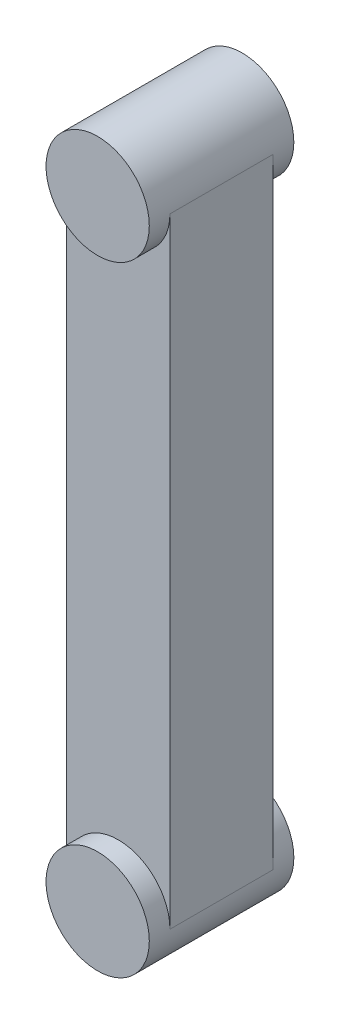
SolidWorks part; units mm, degrees
material "普通碳钢"
ref_plane "前视基准面" through (0, 0, 0) normal (0, 0, 1) x (1, 0, 0)
ref_plane "上视基准面" through (0, 0, 0) normal (0, 1, 0) x (1, 0, 0)
ref_plane "右视基准面" through (0, 0, 0) normal (1, 0, 0) x (0, 0, -1)
sketch "草图1" plane through (0, 0, 0) normal (0, 0, 1) x (1, 0, 0)
  circle A0 centre (0, 0) radius 25
  dimension "D1" = 50
extrude "凸台-拉伸1" add sketch "草图1" along normal blind 35 and the other way blind 35
sketch "草图2" plane through (0, 0, 0) normal (0, 1, 0) x (1, 0, 0)
  line L0 (-25, 25) -> (25, 25)
  line L1 (-25, 35) -> (-25, -35) construction
  line L2 (25, -35) -> (25, 35) construction
  line L3 (25, 25) -> (25, -25)
  line L4 (25, -25) -> (-25, -25)
  line L5 (-25, -25) -> (-25, 25)
  dimension "D1" = 25
  dimension "D2" = 25
extrude "凸台-拉伸2" add sketch "草图2" along normal blind 300
sketch "草图3" plane through (0, 0, 0) normal (0, 0, 1) x (1, 0, 0)
  line L0 (-25, 300) -> (25, 300) construction
  circle A0 centre (0, 300) radius 25
extrude "凸台-拉伸3" add sketch "草图3" along normal blind 35 and the other way blind 35
